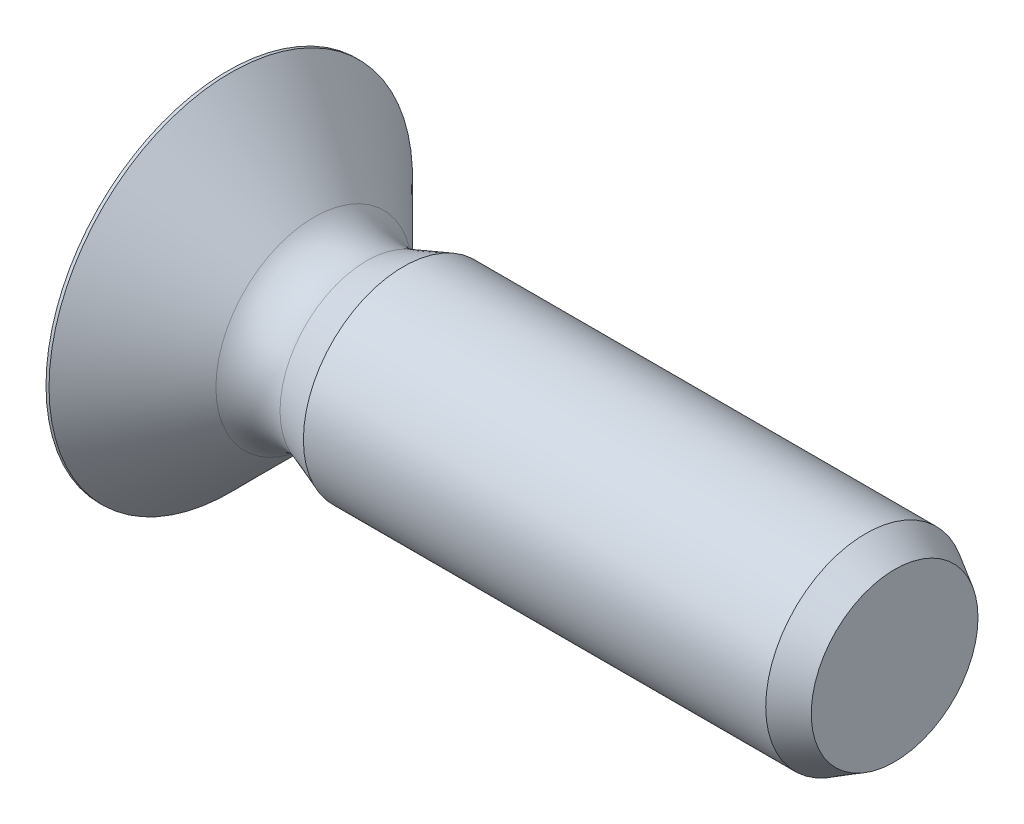
SolidWorks part; units mm, degrees
ref_plane "Front" through (0, 0, 0) normal (0, 0, 1) x (1, 0, 0)
ref_plane "Top" through (0, 0, 0) normal (0, 1, 0) x (1, 0, 0)
ref_plane "Right" through (0, 0, 0) normal (1, 0, 0) x (0, 0, -1)
sketch "Sketch1" plane through (0, 0, 0) normal (0, 0, 1) x (1, 0, 0)
  line L0 (-38.1054, 0) -> (11.3165, 0) construction
  line L1 (21.309, 0) -> (21.309, 3)
  line L2 (21.309, 3) -> (6.5779, 3)
  line L3 (6.5779, 3) -> (4.5779, 2.2721)
  line L4 (4.5779, 2.2721) -> (1.4, 5.45)
  line L5 (21.309, 0) -> (0, 0)
  line L6 (1.4, 5.45) -> (1.309, 5.45)
  line L7 (1.309, 5.45) -> (1.309, 0) construction
  arc A0 (1.309, 5.45) -> (0, 0) centre (12, 0) ccw
  dimension "rf" = 12
  dimension "l" = 20
  dimension "D1" = 45
  dimension "D2" = 20
  dimension "dk" = 10.9
revolve "Base" add sketch "Sketch1" angle 360 about L0
cosmetic thread "ThreadCosmetic1" [suppressed] parameters "D2"=5
sketch "Sketch2" plane through (0, 0, 0) normal (0, 1, 0) x (1, 0, 0)
  line L0 (22.6372, 0) -> (0, 0) construction
  line L1 (21.309, -3) -> (21.309, 3) construction
  line L2 (20.443, -3) -> (21.309, -2.5)
  line L6 (21.309, -2.5) -> (21.309, -3)
  line L7 (21.309, -3) -> (20.443, -3)
  dimension "D1" = 30
  dimension "D2" = 5
  dimension "D3" = 6
revolve "BaseEnd" cut sketch "Sketch2" angle 360 about L0
sketch "Sketch3" plane through (0, 0, 0) normal (-1, 0, 0) x (0, 0, 1)
  line L0 (0, 0) -> (-3.9695, 0) construction
  line L1 (0, 0) -> (0, 3.5828) construction
  line L2 (0.73, 3.65) -> (-0.73, 3.65)
  line L3 (-0.73, 3.65) -> (-0.73, 0.73)
  line L4 (-0.73, 0.73) -> (-3.65, 0.73)
  line L5 (-3.65, 0.73) -> (-3.65, -0.73)
  line L6 (-0.73, -0.73) -> (-3.65, -0.73)
  line L7 (-0.73, -3.65) -> (-0.73, -0.73)
  line L8 (0.73, -3.65) -> (-0.73, -3.65)
  line L9 (0.73, -3.65) -> (0.73, -0.73)
  line L10 (0.73, -0.73) -> (3.65, -0.73)
  line L11 (3.65, 0.73) -> (3.65, -0.73)
  line L12 (0.73, 0.73) -> (3.65, 0.73)
  line L13 (0.73, 3.65) -> (0.73, 0.73)
  point P4 (3.65, 0)
  point P10 (-3.65, 0)
  point P14 (0, -3.65)
  point P19 (0, 3.65)
  dimension "D2" = 1.46
extrude "CrossRecess" cut sketch "Sketch3" against normal blind 2.725
draft "Draft1" type of draft neutral plane draft angle 45 neutral plane "Right" faces to draft 4 face at (1.6526, 0, 3.65) face at (1.6526, 3.65, 0) face at (1.6526, -3.65, 0) face at (1.6526, 0, -3.65) neutral plane through (0, 0, 0) neutral plane normal (1, 0, 0) reverse direction yes parameters "D1"=45
fillet "Fillet1" radius 1.5 1 edges at (4.5779, 0, 2.2721)
sketch "Sketch6" plane through (0, 0, 0) normal (0, 1, 0) x (1, 0, 0)
  line L0 (0, 0) -> (23.9872, 0) construction
  line L1 (20.4359, 3.0141) -> (20.45, 3.0141)
  line L2 (20.45, 3.0141) -> (20.45, 3)
  line L3 (20.45, 3) -> (20.443, 2.9878)
  line L4 (20.443, 2.9878) -> (20.4359, 3)
  line L5 (20.4359, 3) -> (20.4359, 3.0141)
  line L6 (20.443, 3) -> (20.443, -3) construction
  dimension "D1" = 6
  dimension "D2" = 2.9878
revolve "Cut-Revolve10" [suppressed] cut sketch "Sketch6" angle 360 about L0
pattern_linear "LPattern10" [suppressed] count 912 spacing 0.0183 along (-1, 0, 0) of bodies 105
sketch "Sketch5" plane through (0, 0, 0) normal (0, 1, 0) x (1, 0, 0)
  line L0 (15.3245, 0) -> (-0.2214, 0) construction
  line L2 (3.8622, 2.9878) -> (10.1963, 2.9878)
  line L3 (10.1963, 2.9878) -> (11.4864, 3)
  line L5 (11.4864, 3) -> (3.85, 3)
  line L6 (3.85, 3) -> (3.8622, 2.9878)
  line L10 (21.309, -2.5) -> (21.309, 2.5) construction
  line L11 (1.4, -5.45) -> (1.4, 5.45) construction
  dimension "D1" = 2.9878
  dimension "b" = 9.8226
  dimension "D3" = 6
  dimension "D4" = 45
  dimension "D5" = 2.4622
revolve "Cut-Revolve2" [suppressed] cut sketch "Sketch5" angle 360 about L0
equation "\"D2@ThreadCosmetic1\" = \"d@Sketch1\" - 1"
equation "\"D2@Sketch2\" = \"D2@ThreadCosmetic1\""
equation "\"D3@Sketch2\" = \"d@Sketch1\""
equation "\"D2@Sketch3\" = \"m@Sketch3\" / 5"
equation "\"D1@Sketch5\" = \"d@Sketch1\" / 2 - \"a@Sketch1\" * tan ( 3.14 / 9 ) "
equation "\"D1@CrossRecess\" = \"dk@Sketch1\" /4"
equation "\"D1@Sketch6\" = \"d@Sketch1\""
equation "\"D2@Sketch6\" =  \"d@Sketch1\" / 2 - \"a@Sketch1\" * tan ( 3.14 / 9 ) "
equation "\"D3@LPattern10\" =  ( \"D1@Sketch6\" / 2 - \"D2@Sketch6\" )  * 1.5"
equation "\"D1@LPattern10\" =  ( \"l@Sketch1\" -  ( \"dk@Sketch1\" - \"d@Sketch1\" )  / 2 - (  \"D3@Sketch2\" - \"D2@Sketch2\" )  / 2 * 1.732 )  / \"D3@LPattern10\" - 1"
equation "\"D3@Sketch5\" = \"d@Sketch1\""
equation "\"D5@Sketch5\" =   \"dk@Sketch1\" / 2 - \"D1@Sketch5\""
